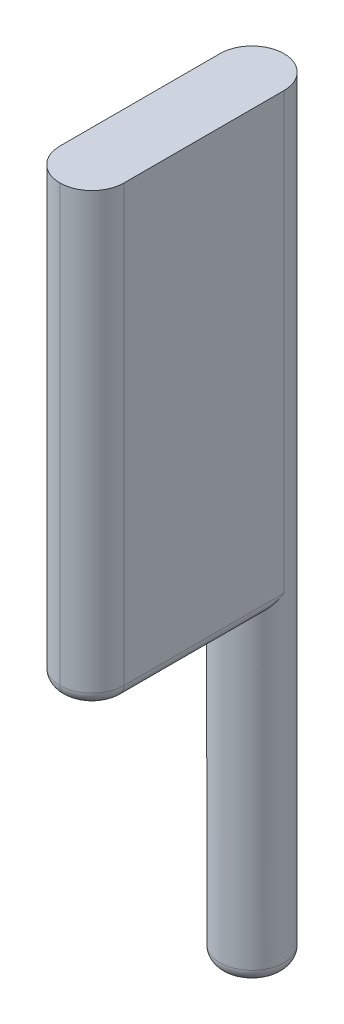
SolidWorks part; units mm, degrees
ref_plane "Front Plane" through (0, 0, 0) normal (0, 0, 1) x (1, 0, 0)
ref_plane "Top Plane" through (0, 0, 0) normal (0, 1, 0) x (1, 0, 0)
ref_plane "Right Plane" through (0, 0, 0) normal (1, 0, 0) x (0, 0, -1)
sketch "Sketch1" plane through (0, 0, 0) normal (0, 1, 0) x (1, 0, 0)
  circle A0 centre (0, 0) radius 5
  dimension "D1" = 10
extrude "Boss-Extrude1" add sketch "Sketch1" along normal blind 50
sketch "Sketch2" plane through (0, 50, 0) normal (0, 1, 0) x (1, 0, 0)
  line L0 (-5, 0) -> (-5, -30)
  line L1 (-5, -30) -> (5, -30)
  line L2 (5, -30) -> (5, 0)
  circle A0 centre (0, 0) radius 5 construction
  arc A1 (-5, 0) -> (5, 0) centre (0, 0) cw
  dimension "D2" = 5
  dimension "30" = 30
extrude "Boss-Extrude2" add sketch "Sketch2" along normal blind 70
fillet "Fillet1" radius 5 2 edges at (-5, 85, 30) (5, 85, 30)
fillet "Fillet2" radius 2 4 edges at (-5, 50, 12.5) (-3.5355, 50, 28.5355) (3.5355, 50, 28.5355) (5, 50, 12.5)
fillet "Fillet3" radius 2 1 edges at (0, 0, 5)
